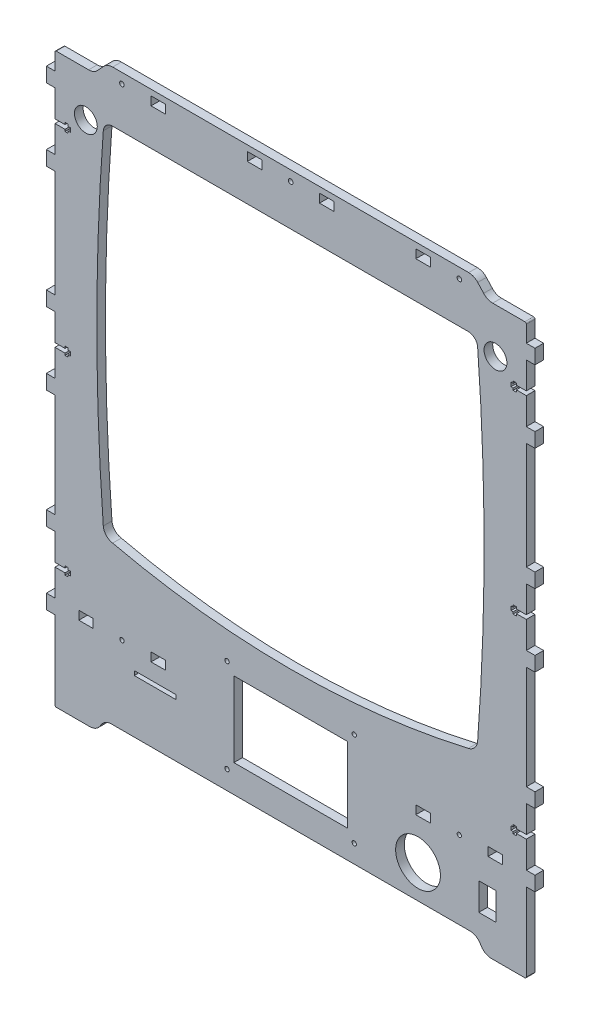
SolidWorks part; units mm, degrees
ref_plane "Спереди" through (0, 0, 0) normal (0, 0, 1) x (1, 0, 0)
ref_plane "Сверху" through (0, 0, 0) normal (0, 1, 0) x (1, 0, 0)
ref_plane "Справа" through (0, 0, 0) normal (1, 0, 0) x (0, 0, -1)
sketch "Эскиз1" plane through (0, 0, 0) normal (0, 0, 1) x (1, 0, 0)
  line L0 (-95.8892, 197.3491) -> (-85.8892, 197.3491)
  line L1 (-85.8892, 197.3491) -> (-85.8892, 191.3491)
  line L2 (-85.8892, 191.3491) -> (-95.8892, 191.3491)
  line L3 (-95.8892, 191.3491) -> (-95.8892, 197.3491)
  line L4 (97.3908, 191.3491) -> (87.3908, 191.3491)
  line L5 (87.3908, 191.3491) -> (87.3908, 197.3491)
  line L6 (87.3908, 197.3491) -> (97.3908, 197.3491)
  line L7 (97.3908, 197.3491) -> (97.3908, 191.3491)
  line L8 (97.3654, -141.9477) -> (87.3654, -141.9477)
  line L9 (87.3654, -141.9477) -> (87.3654, -135.9477)
  line L10 (87.3654, -135.9477) -> (97.3654, -135.9477)
  line L11 (97.3654, -135.9477) -> (97.3654, -141.9477)
  line L12 (147.3854, -141.9477) -> (137.3854, -141.9477)
  line L13 (137.3854, -141.9477) -> (137.3854, -135.9477)
  line L14 (137.3854, -135.9477) -> (147.3854, -135.9477)
  line L15 (147.3854, -135.9477) -> (147.3854, -141.9477)
  line L16 (-135.8946, -141.9477) -> (-145.8946, -141.9477)
  line L17 (-145.8946, -141.9477) -> (-145.8946, -135.9477)
  line L18 (-145.8946, -135.9477) -> (-135.8946, -135.9477)
  line L19 (-135.8946, -135.9477) -> (-135.8946, -141.9477)
  line L20 (-85.8746, -141.9477) -> (-95.8746, -141.9477)
  line L21 (-95.8746, -141.9477) -> (-95.8746, -135.9477)
  line L22 (-95.8746, -135.9477) -> (-85.8746, -135.9477)
  line L23 (-85.8746, -135.9477) -> (-85.8746, -141.9477)
  line L24 (-19.2392, 191.3491) -> (-29.2392, 191.3491)
  line L25 (-29.2392, 191.3491) -> (-29.2392, 197.3491)
  line L26 (-29.2392, 197.3491) -> (-19.2392, 197.3491)
  line L27 (-19.2392, 197.3491) -> (-19.2392, 191.3491)
  line L28 (30.7408, 191.3491) -> (20.7408, 191.3491)
  line L29 (20.7408, 191.3491) -> (20.7408, 197.3491)
  line L30 (20.7408, 197.3491) -> (30.7408, 197.3491)
  line L31 (30.7408, 197.3491) -> (30.7408, 191.3491)
  line L32 (-122.3991, 165.873) -> (123.6241, 165.873)
  line L33 (40.0454, -173.6357) -> (40.0454, -121.6361)
  line L34 (40.0454, -121.6361) -> (-38.5546, -121.6361)
  line L35 (-38.5546, -121.6361) -> (-38.5546, -173.6357)
  line L36 (-38.5546, -173.6357) -> (40.0454, -173.6357)
  line L37 (142.9388, -159.6762) -> (142.9388, -178.6762)
  line L38 (142.9388, -178.6762) -> (130.9388, -178.6762)
  line L39 (130.9388, -178.6762) -> (130.9388, -159.6762)
  line L40 (130.9388, -159.6762) -> (142.9388, -159.6762)
  line L41 (-162.3492, -146.9309) -> (-168.3546, -146.9309)
  line L42 (-168.3546, -146.9309) -> (-168.3546, -136.9309)
  line L43 (-168.3546, -136.9309) -> (-162.3546, -136.9309)
  line L44 (-162.3546, -136.9309) -> (-162.3546, -118.3209)
  line L45 (-162.3546, -96.9409) -> (-168.3546, -96.9409)
  line L46 (-168.3546, -96.9409) -> (-168.3546, -86.9409)
  line L47 (-168.3546, -86.9409) -> (-162.3546, -86.9409)
  line L48 (-162.3546, -86.9409) -> (-162.3546, -15.2109)
  line L49 (-162.3546, -15.2109) -> (-168.3546, -15.2109)
  line L50 (-162.3546, 34.7891) -> (-168.3546, 34.7891)
  line L51 (-168.3546, -5.2109) -> (-162.3546, -5.2109)
  line L52 (-168.3546, 44.7891) -> (-162.3546, 44.7891)
  line L56 (-162.3546, 128.9491) -> (-162.3546, 147.5491)
  line L57 (-162.3492, 168.9491) -> (-168.3492, 168.9491)
  line L58 (-168.3492, 168.9491) -> (-168.3492, 178.9491)
  line L59 (-168.3492, 178.9491) -> (-162.3492, 178.9491)
  line L60 (-162.3492, 178.9491) -> (-162.3492, 190.3491)
  line L61 (-162.3492, -200.9709) -> (-162.3492, -146.9309)
  line L62 (163.8454, -146.9309) -> (169.8454, -146.9309)
  line L63 (169.8454, -146.9309) -> (169.8454, -136.9309)
  line L64 (169.8454, -136.9309) -> (163.8513, -136.9309)
  line L65 (163.8513, -136.9309) -> (163.8513, -118.3209)
  line L66 (163.9392, -96.9409) -> (169.8512, -96.9409)
  line L67 (169.8512, -96.9409) -> (169.8512, -86.9409)
  line L68 (169.8512, -86.9409) -> (163.8512, -86.9409)
  line L69 (163.8512, -86.9409) -> (163.8512, -15.2109)
  line L70 (163.8512, -15.2109) -> (169.8512, -15.2109)
  line L71 (163.8512, 34.7891) -> (169.8512, 34.7891)
  line L72 (169.8512, -5.2109) -> (163.8512, -5.2109)
  line L73 (169.8512, 44.7891) -> (163.8512, 44.7891)
  line L74 (163.8512, 118.9491) -> (169.8512, 118.9491)
  line L75 (169.8512, 118.9491) -> (169.8512, 128.9491)
  line L76 (169.8512, 128.9491) -> (163.8512, 128.9491)
  line L77 (163.8512, 128.9491) -> (163.8512, 147.5491)
  line L78 (163.8508, 168.9491) -> (169.8508, 168.9491)
  line L79 (169.8508, 168.9491) -> (169.8508, 178.9491)
  line L80 (169.8508, 178.9491) -> (163.8508, 178.9491)
  line L81 (163.8508, 178.9491) -> (163.8508, 190.3491)
  line L82 (156.9388, 150.3491) -> (156.9388, 151.7492)
  line L83 (163.9392, -115.5209) -> (156.9392, -115.5209)
  line L84 (156.9392, -114.1224) -> (154.7382, -114.1224)
  line L85 (156.9399, -118.3209) -> (163.8513, -118.3209)
  line L86 (153.2384, -118.3222) -> (154.7405, -118.3222)
  line L87 (-155.4441, 11.989) -> (-153.2432, 11.989)
  line L88 (154.7382, -114.1224) -> (154.7382, -115.5222)
  line L89 (154.7391, 16.1893) -> (153.24, 16.1893)
  line L90 (153.2384, -115.5222) -> (153.2384, -118.3222)
  line L91 (-155.4426, -119.721) -> (-153.2418, -119.721)
  line L92 (163.8508, 150.3491) -> (156.9388, 150.3491)
  line L93 (156.9399, -119.7231) -> (156.9399, -118.3209)
  line L94 (156.9392, -115.5209) -> (156.9392, -114.1224)
  line L95 (154.7382, -115.5222) -> (153.2384, -115.5222)
  line L96 (154.741, 147.5502) -> (154.741, 146.1493)
  line L97 (-155.4451, -114.1209) -> (-155.4451, -115.5209)
  line L98 (154.7415, 13.3902) -> (154.7415, 11.9893)
  line L99 (-162.3546, 147.5491) -> (-155.4441, 147.5491)
  line L100 (-155.4441, 147.5491) -> (-155.4441, 146.149)
  line L101 (-155.4398, 150.3491) -> (-162.3492, 150.3491)
  line L102 (-153.2398, 150.3482) -> (-153.2398, 151.7491)
  line L103 (154.7405, -118.3222) -> (154.7405, -119.7231)
  line L104 (-155.4451, -115.5209) -> (-162.3546, -115.5209)
  line L105 (154.741, 151.7492) -> (154.741, 150.3493)
  line L106 (156.9417, 146.1493) -> (156.9417, 147.5491)
  line L107 (-153.2432, 13.3622) -> (-151.7428, 13.3622)
  line L108 (-155.4426, -118.3209) -> (-155.4426, -119.721)
  line L109 (153.241, 150.3493) -> (153.241, 147.5502)
  line L110 (-153.2451, 17.5891) -> (-155.4451, 17.5891)
  line L111 (-162.3546, 13.3891) -> (-155.4441, 13.3891)
  line L112 (154.741, 146.1493) -> (156.9417, 146.1493)
  line L113 (153.241, 147.5502) -> (154.741, 147.5502)
  line L114 (-153.2433, 147.5489) -> (-151.7375, 147.5489)
  line L115 (-151.7428, 13.3622) -> (-151.7428, 16.1885)
  line L116 (163.8512, 16.1891) -> (156.9392, 16.1891)
  line L117 (154.7391, 17.5621) -> (154.7391, 16.1893)
  line L118 (154.741, 150.3493) -> (153.241, 150.3493)
  line L119 (154.7415, 11.9893) -> (156.9417, 11.9893)
  line L120 (-153.2451, -114.1209) -> (-155.4451, -114.1209)
  line L121 (-151.7436, -118.3211) -> (-151.7436, -115.5218)
  line L122 (-153.2418, -118.3211) -> (-151.7436, -118.3211)
  line L123 (-153.2432, 11.989) -> (-153.2432, 13.3622)
  line L124 (156.9417, 13.3891) -> (163.8512, 13.3891)
  line L125 (-162.3546, -118.3209) -> (-155.4426, -118.3209)
  line L126 (153.24, 16.1893) -> (153.24, 13.3902)
  line L127 (-153.2451, -115.5218) -> (-153.2451, -114.1209)
  line L128 (-151.7428, 16.1885) -> (-153.2451, 16.1885)
  line L129 (-155.4441, 146.149) -> (-153.2433, 146.149)
  line L130 (-153.2418, -119.721) -> (-153.2418, -118.3211)
  line L131 (-155.4398, 151.7491) -> (-155.4398, 150.3491)
  line L132 (-151.7436, -115.5218) -> (-153.2451, -115.5218)
  line L133 (-153.2433, 146.149) -> (-153.2433, 147.5489)
  line L134 (153.24, 13.3902) -> (154.7415, 13.3902)
  line L135 (156.9388, 151.7492) -> (154.741, 151.7492)
  line L136 (-151.7375, 147.5489) -> (-151.738, 150.3482)
  line L137 (156.9417, 147.5491) -> (163.8512, 147.5491)
  line L138 (-155.4451, 16.1891) -> (-162.3546, 16.1891)
  line L139 (156.9417, 11.9893) -> (156.9417, 13.3891)
  line L140 (-155.4451, 17.5891) -> (-155.4451, 16.1891)
  line L141 (154.7405, -119.7231) -> (156.9399, -119.7231)
  line L142 (-153.2398, 151.7491) -> (-155.4398, 151.7491)
  line L143 (156.9392, 17.5621) -> (154.7391, 17.5621)
  line L144 (-151.738, 150.3482) -> (-153.2398, 150.3482)
  line L145 (-162.3546, -115.5209) -> (-162.3546, -96.9409)
  line L146 (-162.3492, 150.3491) -> (-162.3492, 168.9491)
  line L147 (163.9392, -115.5209) -> (163.9392, -96.9409)
  line L148 (163.8508, 150.3491) -> (163.8508, 168.9491)
  line L149 (-139.0924, 191.3491) -> (-161.5253, 191.3491)
  line L150 (-128.7242, 198.5879) -> (-132.8221, 194.1104)
  line L151 (123.9554, 201.3491) -> (-122.4539, 201.3491)
  line L152 (130.2257, 198.5879) -> (134.3236, 194.1104)
  line L153 (140.5939, 191.3491) -> (162.8508, 191.3491)
  line L154 (-131.8015, -198.9146) -> (-129.7448, -195.8949)
  line L155 (162.7628, -201.9477) -> (139.7264, -201.9477)
  line L156 (133.303, -198.9146) -> (131.2463, -195.8949)
  line L157 (-161.4373, -201.9509) -> (-138.3129, -201.9509)
  line L158 (-123.2334, -192.8586) -> (124.7349, -192.8586)
  line L159 (163.8454, -200.9731) -> (163.8454, -146.9309)
  line L160 (-162.3546, 13.3891) -> (-162.3546, -5.2109)
  line L161 (-168.3546, -15.2109) -> (-168.3546, -5.2109)
  line L162 (-168.3546, 34.7891) -> (-168.3546, 44.7891)
  line L163 (-162.3546, 44.7891) -> (-162.3546, 118.9491)
  line L164 (163.8512, 13.3891) -> (163.8512, -5.2109)
  line L165 (169.8512, -15.2109) -> (169.8512, -5.2109)
  line L166 (169.8512, 34.7891) -> (169.8512, 44.7891)
  line L167 (163.8512, 44.7891) -> (163.8512, 118.9491)
  line L168 (-155.4441, 13.3891) -> (-155.4441, 11.989)
  line L169 (-153.2451, 16.1885) -> (-153.2451, 17.5891)
  line L170 (156.9392, 16.1891) -> (156.9392, 17.5621)
  line L171 (-162.3546, 34.7891) -> (-162.3546, 16.1891)
  line L172 (163.8512, 34.7891) -> (163.8512, 16.1891)
  line L173 (-107.5042, -155.9271) -> (-107.5042, -152.9271)
  line L174 (-107.5042, -152.9271) -> (-78.5042, -152.9271)
  line L175 (-78.5042, -152.9271) -> (-78.5042, -155.9271)
  line L176 (-78.5042, -155.9271) -> (-107.5042, -155.9271)
  line L177 (-162.3546, 128.9491) -> (-168.3546, 128.9491)
  line L178 (-162.3546, 118.9491) -> (-168.3546, 118.9491)
  line L179 (-168.3546, 118.9491) -> (-168.3546, 128.9491)
  line L180 (-155.4426, -141.9477) -> (156.9399, -141.9477) construction
  arc A0 (-122.4711, -84.0153) -> (123.6489, -84.0153) centre (0.5889, 449.8336) ccw
  arc A1 (-128.9341, 159.8968) -> (-128.9472, -76.974) centre (1428.6282, 41.3753) ccw
  arc A2 (130.1254, -76.9742) -> (130.1588, 159.8968) centre (-1430.5029, 41.6814) ccw
  circle A3 centre (44.7454, -115.1361) radius 1.5
  circle A4 centre (44.7454, -180.3857) radius 1.5
  circle A5 centre (-43.2546, -179.8825) radius 1.5
  circle A6 centre (-43.2546, -115.1361) radius 1.5
  circle A7 centre (88.8942, -169.8279) radius 15.5
  arc A8 (130.1588, 159.8968) -> (123.6241, 165.873) centre (123.6241, 159.3123) ccw
  arc A9 (-122.3991, 165.873) -> (-128.9341, 159.8968) centre (-122.472, 159.3916) ccw
  arc A10 (-128.9472, -76.974) -> (-122.4711, -84.0153) centre (-121.245, -76.3888) ccw
  arc A11 (123.6489, -84.0153) -> (130.1254, -76.9742) centre (121.7477, -75.7674) ccw
  circle A12 centre (0.7508, 194.3491) radius 1.6
  circle A13 centre (-116.0492, 194.3491) radius 1.6
  arc A14 (134.3236, 194.1104) -> (140.5939, 191.3491) centre (140.5939, 199.8491) ccw
  arc A15 (-161.5253, 191.3491) -> (-162.3492, 190.3491) centre (-161.4373, 190.4372) ccw
  arc A16 (-139.0924, 191.3491) -> (-132.8221, 194.1104) centre (-139.0924, 199.8491) ccw
  arc A17 (-122.4539, 201.3491) -> (-128.7242, 198.5879) centre (-122.4539, 192.8491) ccw
  circle A18 centre (117.5508, 194.3491) radius 1.6
  arc A19 (130.2257, 198.5879) -> (123.9554, 201.3491) centre (123.9554, 192.8491) ccw
  arc A20 (163.8508, 190.3491) -> (162.8508, 191.3491) centre (162.8508, 190.3491) ccw
  arc A21 (-123.2334, -192.8586) -> (-129.7448, -195.8949) centre (-123.2334, -201.3586) ccw
  arc A22 (-138.3129, -201.9509) -> (-131.8015, -198.9146) centre (-138.3129, -193.4509) ccw
  arc A23 (131.2463, -195.8949) -> (124.7349, -192.8586) centre (124.7349, -201.3586) ccw
  arc A24 (133.303, -198.9146) -> (139.7264, -201.9477) centre (139.7677, -193.542) ccw
  arc A25 (-162.3492, -200.9709) -> (-161.4373, -201.9509) centre (-161.3926, -200.9949) ccw
  arc A26 (162.7628, -201.9477) -> (163.8454, -200.9731) centre (162.8028, -200.9035) ccw
  circle A27 centre (-140.9992, 160.3491) radius 7.9
  circle A28 centre (142.5008, 160.3491) radius 7.9
  circle A29 centre (-115.9946, -138.9477) radius 1.5
  circle A30 centre (117.4854, -138.9477) radius 1.5
  point P239 (87.3908, 194.3491)
  point P241 (-162.3492, 184.6491)
  point P244 (-140.8946, -141.9477)
  dimension "D11" = 15.8
  dimension "D12" = 15.8
  dimension "D53" = 31
  dimension "D88" = 283.5
  dimension "D1" = 10
  dimension "D2" = 12.4
  dimension "D3" = 12.4
  dimension "D4" = 10
  dimension "D5" = 18.6
  dimension "D6" = 2.8
  dimension "D7" = 18.6
  dimension "D8" = 10
  dimension "D9" = 10
  dimension "D10" = 10
  dimension "D13" = 6
  dimension "D14" = 18.6
  dimension "D15" = 18.6
  dimension "D16" = 10
  dimension "D17" = 74.16
  dimension "D18" = 74.16
  dimension "D19" = 10
  dimension "D20" = 10
  dimension "D21" = 18.6
  dimension "D22" = 18.6
  dimension "D23" = 18.6
  dimension "D24" = 18.6
  dimension "D25" = 10
  dimension "D26" = 10
  dimension "D27" = 71.73
  dimension "D28" = 71.73
  dimension "D29" = 10
  dimension "D30" = 10
  dimension "D31" = 18.58
  dimension "D32" = 18.58
  dimension "D33" = 18.61
  dimension "D34" = 18.61
  dimension "D35" = 10
  dimension "D36" = 10
  dimension "D37" = 54.04
  dimension "D38" = 54.0422
  dimension "D39" = 403.2968
  dimension "D40" = 2.8
  dimension "D41" = 2.8
  dimension "D42" = 2.8
  dimension "D43" = 2.8
  dimension "D44" = 403.3
  dimension "D45" = 10
  dimension "D46" = 10
  dimension "D47" = 10
  dimension "D48" = 169.1
  dimension "D49" = 10
  dimension "D50" = 10
  dimension "D51" = 10
  dimension "D52" = 10
  dimension "D54" = 338.2
  dimension "D55" = 169.1
  dimension "D56" = 10
  dimension "D57" = 52.3
  dimension "D58" = 52.3
  dimension "D59" = 72.46
  dimension "D60" = 72.46
  dimension "D61" = 56.65
  dimension "D62" = 56.65
  dimension "D63" = 19.99
  dimension "D64" = 19.99
  dimension "D65" = 21.35
  dimension "D66" = 21.35
  dimension "D67" = 22.46
  dimension "D68" = 22.46
  dimension "D69" = 19.9
  dimension "D70" = 19.9
  dimension "D71" = 20.12
  dimension "D72" = 20.12
  dimension "D73" = 47.32
  dimension "D74" = 78.6
  dimension "D75" = 47.32
  dimension "D76" = 4.7
  dimension "D77" = 4.7
  dimension "D78" = 4.7
  dimension "D79" = 4.7
  dimension "D80" = 6.5
  dimension "D81" = 6.5
  dimension "D82" = 6
  dimension "D83" = 60
  dimension "D84" = 55.02
  dimension "D85" = 6
  dimension "D86" = 29
  dimension "D87" = 3
  dimension "D89" = 4
  dimension "D90" = 7
  dimension "D91" = 6
  dimension "D92" = 4
  dimension "D93" = 6
  dimension "D94" = 7
  dimension "D95" = 4
  dimension "D96" = 6
  dimension "D97" = 4
  dimension "D98" = 2.8
  dimension "D99" = 7
  dimension "D100" = 31
  dimension "D101" = 31
  dimension "D102" = 166.56
  dimension "D103" = 131.73
  dimension "D104" = 51.9996
  dimension "D105" = 6
  dimension "D106" = 3
  dimension "D107" = 6
  dimension "D108" = 3
  dimension "D109" = 6
  dimension "D111" = 6
  dimension "D114" = 326.2
extrude "Бобышка-Вытянуть2" add sketch "Эскиз1" along normal blind 6 contours A5 | A4 | A3 | A13 | A12 | A7 | A6 | L32 A8 A2 A11 A0 A10 A1 A9 | A18 | A30 | A29 | A28 | A27 | L4 L5 L6 L7 | L0 L1 L2 L3 | L20 L21 L22 L23 | L16 L17 L18 L19 | L12 L13 L14 L15 | L8 L9 L10 L11 | L37 L38 L39 L40 | L33 L34 L35 L36 | L28 L29 L30 L31 | L24 L25 L26 L27 | L41 L42 L43 L44 L125 L108 L91 L130 L122 L121 L132 L127 L120 L97 L104 L145 L45 L46 L47 L48 L49 L161 L51 L160 L111 L168 L87 L123 L107 L115 L128 L169 L110 L140 L138 L171 L50 L162 L52 L163 L178 L179 L177 L56 L99 L100 L129 L133 L114 L136 L144 L102 L142 L131 L101 L146 L57 L58 L59 L60 A15 L149 A16 L150 A17 L151 A19 L152 A14 L153 A20 L81 L80 L79 L78 L148 L92 L82 L135 L105 L118 L109 L113 L96 L112 L106 L137 L77 L76 L75 L74 L167 L73 L166 L71 L172 L116 L170 L143 L117 L89 L126 L134 L98 L119 L139 L124 L164 L72 L165 L70 L69 L68 L67 L66 L147 L83 L94 L84 L88 L95 L90 L86 L103 L141 L93 L85 L65 L64 L63 L62 L159 A26 L155 A24 L156 A23 L158 A21 L154 A22 L157 A25 L61 | L173 L174 L175 L176
